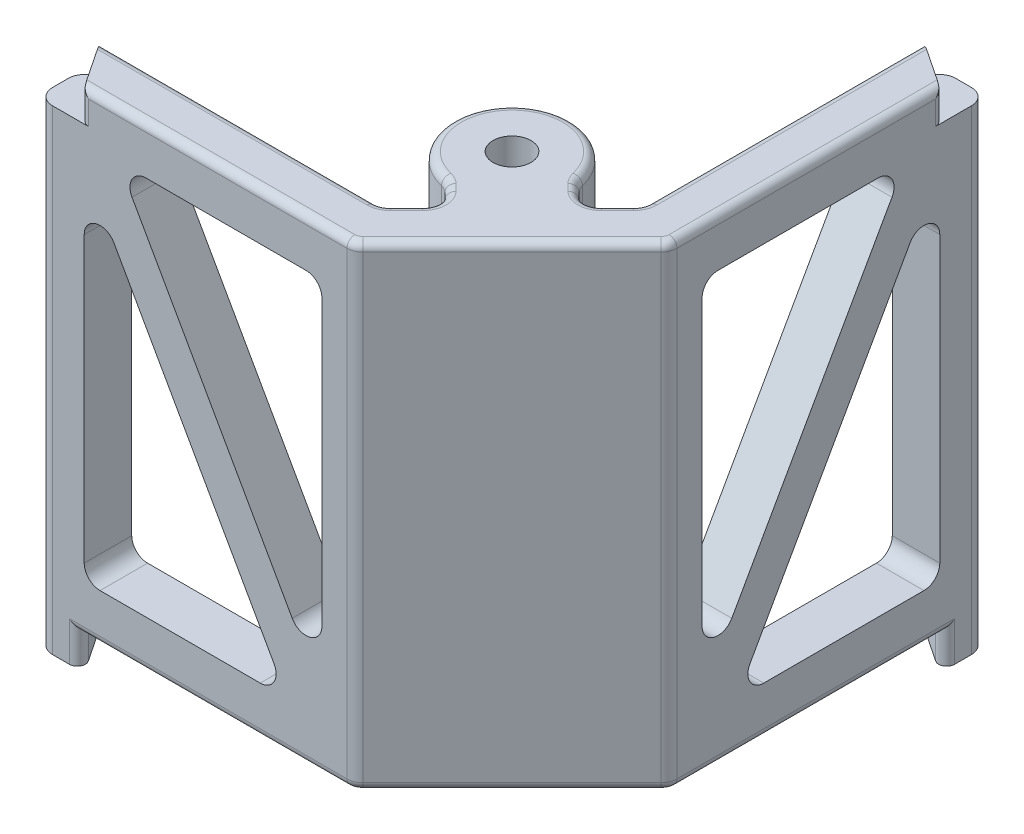
SolidWorks part; units mm, degrees
ref_plane "Front Plane" through (0, 0, 0) normal (0, 0, 1) x (1, 0, 0)
ref_plane "Top Plane" through (0, 0, 0) normal (0, 1, 0) x (1, 0, 0)
ref_plane "Right Plane" through (0, 0, 0) normal (1, 0, 0) x (0, 0, -1)
sketch "Sketch1" plane through (0, 0, 0) normal (0, 1, 0) x (1, 0, 0)
  line L0 (10, 0) -> (10, 19)
  line L1 (9, 20) -> (8, 20)
  line L3 (-19, -10) -> (0, -10)
  line L4 (-20, -8) -> (-20, -9)
  line L6 (10, 0) -> (0, -10)
  line L7 (0, -10) -> (0, 0) construction
  line L8 (0, 0) -> (10, 0) construction
  line L9 (-19, -7) -> (-1.2426, -7)
  line L10 (7, 19) -> (7, 1.2426)
  line L11 (7, 1.2426) -> (5, -0.7574)
  line L12 (0, 0) -> (11.2106, -11.2106) construction
  line L13 (3.6527, 0.59) -> (5, -0.7574)
  line L14 (-0.59, -3.6527) -> (0.7574, -5)
  line L15 (0.7574, -5) -> (-1.2426, -7)
  circle A1 centre (0, 0) radius 1.2 construction
  circle A3 centre (0, 0) radius 1.2
  arc A5 (3.6527, 0.59) -> (-0.59, -3.6527) centre (0, 0) ccw
  arc A6 (10, 19) -> (9, 20) centre (9, 19) ccw
  arc A7 (8, 20) -> (7, 19) centre (8, 19) ccw
  arc A8 (-19, -10) -> (-20, -9) centre (-19, -9) cw
  arc A9 (-20, -8) -> (-19, -7) centre (-19, -8) cw
  circle A10 centre (0, 0) radius 3.7 construction
  point P22 (10, 20)
  point P25 (7, 20)
  point P28 (-20, -10)
  point P31 (-20, -7)
  dimension "D5" = 3
  dimension "D2" = 3
  dimension "D8" = 3
  dimension "D9" = 1
  dimension "D6" = 2.5
  dimension "D1" = 30
  dimension "D3" = 30
  dimension "D4" = 3
  dimension "D7" = 14.1421
extrude "Boss-Extrude1" add sketch "Sketch1" along normal blind 30
sketch "Sketch5" plane through (0, 0, 0) normal (0, -1, 0) x (1, 0, 0)
  line L0 (-17, 10) -> (-19, 7)
  line L1 (-19, 10) -> (0, 10) construction
  line L2 (-20, 8) -> (-20, 9) construction
  line L3 (-19, 10) -> (-17, 10)
  line L4 (-20, 8) -> (-20, 9)
  line L5 (12.7211, 12.7211) -> (-11.6424, -11.6424) construction
  line L6 (0, 10) -> (10, 0) construction
  line L7 (8, -20) -> (9, -20)
  line L8 (10, -19) -> (10, -17)
  line L9 (10, -17) -> (7, -19)
  arc A0 (-20, 8) -> (-19, 7) centre (-19, 8) ccw construction
  arc A1 (-19, 10) -> (-20, 9) centre (-19, 9) ccw construction
  arc A2 (-20, 8) -> (-19, 7) centre (-19, 8) ccw
  arc A3 (-19, 10) -> (-20, 9) centre (-19, 9) ccw
  arc A4 (10, -19) -> (9, -20) centre (9, -19) cw
  arc A5 (8, -20) -> (7, -19) centre (8, -19) cw
  point P13 (5, 5)
  dimension "D1" = 3
extrude "Boss-Extrude3" add sketch "Sketch5" along normal blind 2
sketch "Sketch6" plane through (0, 30, 0) normal (0, 1, 0) x (1, 0, 0)
  line L0 (10, 19) -> (10, 17) construction
  line L1 (10, 17) -> (7, 19) construction
  line L2 (8, 20) -> (9, 20) construction
  line L3 (-17, -10) -> (-19, -10) construction
  line L4 (-20, -9) -> (-20, -8) construction
  line L5 (-19, -7) -> (-17, -10) construction
  line L6 (10, 19) -> (10, 17)
  line L7 (10, 17) -> (7, 19)
  line L8 (8, 20) -> (9, 20)
  line L9 (-17, -10) -> (-19, -10)
  line L10 (-20, -9) -> (-20, -8)
  line L11 (-19, -7) -> (-17, -10)
  arc A0 (10, 19) -> (9, 20) centre (9, 19) ccw construction
  arc A1 (8, 20) -> (7, 19) centre (8, 19) ccw construction
  arc A2 (-20, -9) -> (-19, -10) centre (-19, -9) ccw construction
  arc A3 (-19, -7) -> (-20, -8) centre (-19, -8) ccw construction
  arc A4 (10, 19) -> (9, 20) centre (9, 19) ccw
  arc A5 (8, 20) -> (7, 19) centre (8, 19) ccw
  arc A6 (-20, -9) -> (-19, -10) centre (-19, -9) ccw
  arc A7 (-19, -7) -> (-20, -8) centre (-19, -8) ccw
extrude "Cut-Extrude2" cut sketch "Sketch6" against normal blind 2
sketch "Sketch2" plane through (0, 0, 10) normal (0, 0, 1) x (1, 0, 0)
  line L1 (-13.1109, 27) -> (-3, 27)
  line L2 (-17, 21.959) -> (-17, 4)
  line L3 (-16, 3) -> (-5.8891, 3)
  line L4 (-2, 26) -> (-2, 8.041)
  line L8 (-13.9823, 25.5094) -> (-3.8714, 7.5504)
  line L9 (-15.1286, 22.4496) -> (-5.0177, 4.4906)
  line L10 (-14.8215, 27) -> (-17, 25.7735) construction
  line L11 (-2, 4.2265) -> (-4.1785, 3) construction
  line L12 (-17, 30) -> (0, 30) construction
  line L13 (-20, 30) -> (-20, 0) construction
  line L14 (-17, 0) -> (0, 0) construction
  line L15 (0, 30) -> (0, 0) construction
  arc A0 (-17, 4) -> (-16, 3) centre (-16, 4) ccw
  arc A1 (-5.0177, 4.4906) -> (-5.8891, 3) centre (-5.8891, 4) cw
  arc A2 (-3.8714, 7.5504) -> (-2, 8.041) centre (-3, 8.041) ccw
  arc A3 (-3, 27) -> (-2, 26) centre (-3, 26) cw
  arc A4 (-13.9823, 25.5094) -> (-13.1109, 27) centre (-13.1109, 26) cw
  arc A5 (-15.1286, 22.4496) -> (-17, 21.959) centre (-16, 21.959) ccw
  dimension "D7" = 1
  dimension "D1" = 3
  dimension "D2" = 3
  dimension "D3" = 3
  dimension "D4" = 2
  dimension "D5" = 2.5
  dimension "D6" = 0
extrude "Cut-Extrude1" cut sketch "Sketch2" against normal up to surface (3 mm away) up to face at (-11.8971, 17.6, 7)
ref_plane "Plane1" through (0, 0, 0) normal (-0.7071, 0, 0.7071) x (0.7071, 0, 0.7071)
mirror "Mirror6" about plane through (0, 0, 0) normal (-0.7071, 0, 0.7071) of face at (-2.8411, 7.4347, 8.5) of face at (-2.3964, 26.6036, 8.5) of face at (-2, 17.0205, 8.5) of face at (-8.0555, 27, 8.5) of face at (-8.9269, 16.5299, 8.5) of face at (-13.7604, 26.3797, 8.5) of face at (-17, 12.9795, 8.5) of face at (-16.6036, 3.3964, 8.5) of face at (-10.9445, 3, 8.5) of face at (-5.2396, 3.6203, 8.5) of face at (-10.0731, 13.4701, 8.5) of face at (-16.1589, 22.5653, 8.5)
fillet "Fillet1" radius 1 8 edges at (10, 15, 0) (0, 15, 10) (3.6527, 15, -0.59) (-1.2426, 15, 7) (5, 15, 0.7574) (7, 15, -1.2426) (0.7574, 15, 5) (-0.59, 15, 3.6527)
fillet "Fillet2" radius 0.5 40 edges at (10, 0, -8.7071) (9.9239, 0, -0.0315) (5, 0, 5) (-0.0315, 0, 9.9239) (-8.7071, 0, 10) (10, 30, -8.7071) (9.9239, 30, -0.0315) (5, 30, 5) (-0.0315, 30, 9.9239) (-8.7071, 30, 10) (-10.3284, 0, 7) (6.2071, 0, -0.4497) (7, 0, -10.3284) (-10.3284, 30, 7) (6.2071, 30, -0.4497) (7, 30, -10.3284) (-1.2742, 0, 6.9239) (-0.4497, 0, 6.2071) (0.3431, 0, 5) (-0.163, 0, 4.0796) (-0.5961, 0, 3.7002) (-2.6163, 0, -2.6163) (3.7002, 0, -0.5961) (4.0796, 0, -0.163) (5, 0, 0.3431) (6.9239, 0, -1.2742) (-1.2742, 30, 6.9239) (-0.4497, 30, 6.2071) (0.3431, 30, 5) (-0.163, 30, 4.0796) (-0.5961, 30, 3.7002) (-2.6163, 30, -2.6163) (3.7002, 30, -0.5961) (4.0796, 30, -0.163) (5, 30, 0.3431) (6.9239, 30, -1.2742) (-17, -1, 10) (10, -1, -17) (10, 29, -17) (-17, 29, 10)
